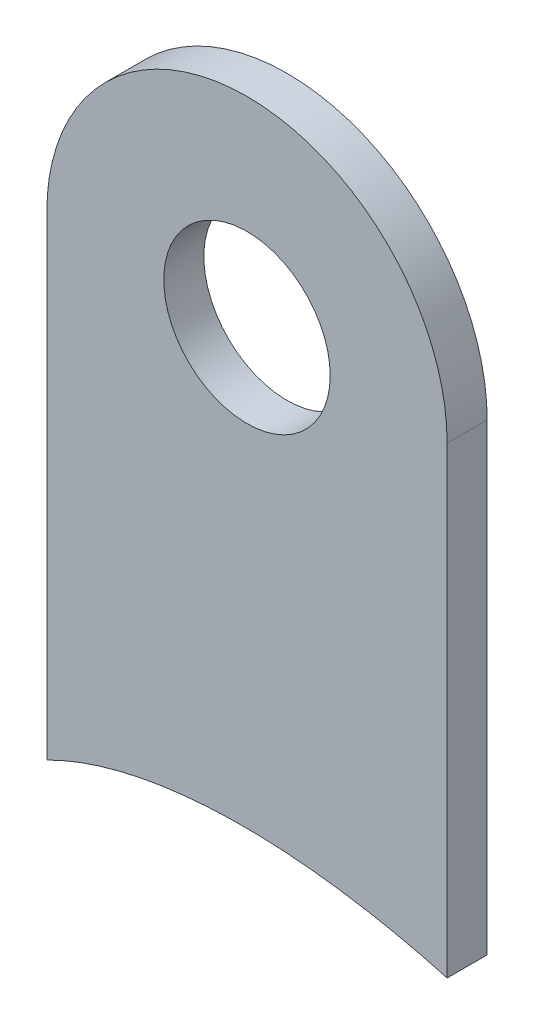
SolidWorks part; units mm, degrees
material "ASTM A36 Steel"
ref_plane "X-Y Datum" through (0, 0, 0) normal (0, 0, 1) x (1, 0, 0)
ref_plane "X-Z Datum" through (0, 0, 0) normal (0, 1, 0) x (1, 0, 0)
ref_plane "Y-Z Datum" through (0, 0, 0) normal (1, 0, 0) x (0, 0, -1)
sketch "Sketch1" plane through (0, 0, 0) normal (0, 0, 1) x (1, 0, 0)
  line L0 (-7.9375, 0) -> (-7.9375, -25.4)
  line L1 (-7.9375, -25.4) -> (7.9375, -25.4)
  line L2 (7.9375, -25.4) -> (7.9375, 0)
  circle A0 centre (0, 0) radius 7.9375
  circle A1 centre (0, 0) radius 3
  dimension "D1" = 6
  dimension "D2" = 15.875
  dimension "D3" = 25.4
extrude "Boss-Extrude1" add sketch "Sketch1" along normal blind 1.5875 contours A0 A1 | A0 L0 L1 L2 | A1 region at (0, -15.7352, 0) region at (0, 7.713, 0) region at (0, 0, 0)
hole_wizard "M6 Clearance Hole1" positions "Sketch2" profile "Sketch3" hole size "M6" standard "ANSI Metric" end condition through all
sketch "Sketch2" plane through (0, 0, 1.5875) normal (0, 0, 1) x (1, 0, 0)
  point P0 (0, 0)
sketch "Sketch3" plane through (0, 0, 1.5875) normal (1, 0, 0) x (0, -1, 0)
  line L0 (0, 0) -> (0, 1.5875)
  line L1 (0, 1.5875) -> (3.3, 1.5875)
  line L2 (3.3, 1.5875) -> (3.3, 0)
  line L5 (3.3, 0) -> (0, 0)
  line L11 (0, -6.35) -> (0, 107.95) construction
  dimension "Thru Hole Dia." = 6.6
  dimension "Thru Hole Depth" = 1.5875
sketch "Sketch4" [suppressed] plane through (0, 0, 2.54) normal (0, 0, 1) x (1, 0, 0)
  line L1 (57.1174, 89.0913) -> (2.6108, -25.4)
  line L3 (1.0953, -29.3967) -> (-107.8628, 152.3221)
  line M3 (-7.9375, 0) -> (-7.9375, -25.4)
  line M4 (-7.9375, -25.4) -> (7.9375, -25.4)
  line M5 (7.9375, -25.4) -> (7.9375, 0)
extrude "Cut-Extrude1" [suppressed] cut sketch "Sketch4" against normal through all contours L3 M4 M3 | L1 M5 M4
sketch "Sketch5" plane through (0, 0, 1.5875) normal (0, 0, 1) x (1, 0, 0)
  line L0 (-7.9375, 0) -> (-7.9375, -25.4) construction
  line L1 (7.9375, -25.4) -> (-7.9375, -25.4)
  line L2 (7.9375, -25.4) -> (7.9375, -19.05)
  line L3 (7.9375, -19.05) -> (-7.9375, -19.05)
  line L4 (-7.9375, -25.4) -> (-7.9375, -19.05)
  dimension "D1" = 6.35
extrude "Cut-Extrude2" cut sketch "Sketch5" against normal through all
sketch "Sketch6" plane through (0, 0, 0) normal (0, 0, -1) x (-1, 0, 0)
  spline S0 degree 3 poles (12.0303, -22.8994) (1.6525, 0.2838) (-38.2843, -17.5937) (-27.9064, -40.7769) (-17.5286, -63.9601) (22.4081, -46.0826) (12.0303, -22.8994) (1.6525, 0.2838) (-38.2843, -17.5937) knots -0.5 0 0 0 0.5 0.5 0.5 1 1 1 1.5 1.5 1.5 weights 1 0.333333 0.333333 1 0.333333 0.333333 1 0.333333 0.333333 only from (12.0303, -22.8994) to (12.0303, -22.8994)
  spline S1 degree 3 poles (12.0303, -22.8994) (1.6525, 0.2838) (-38.2843, -17.5937) (-27.9064, -40.7769) (-17.5286, -63.9601) (22.4081, -46.0826) (12.0303, -22.8994) (1.6525, 0.2838) (-38.2843, -17.5937) knots -0.5 0 0 0 0.5 0.5 0.5 1 1 1 1.5 1.5 1.5 weights 1 0.333333 0.333333 1 0.333333 0.333333 1 0.333333 0.333333 only from (12.0303, -22.8994) to (12.0303, -22.8994)
extrude "Cut-Extrude3" cut sketch "Sketch6" against normal through all
